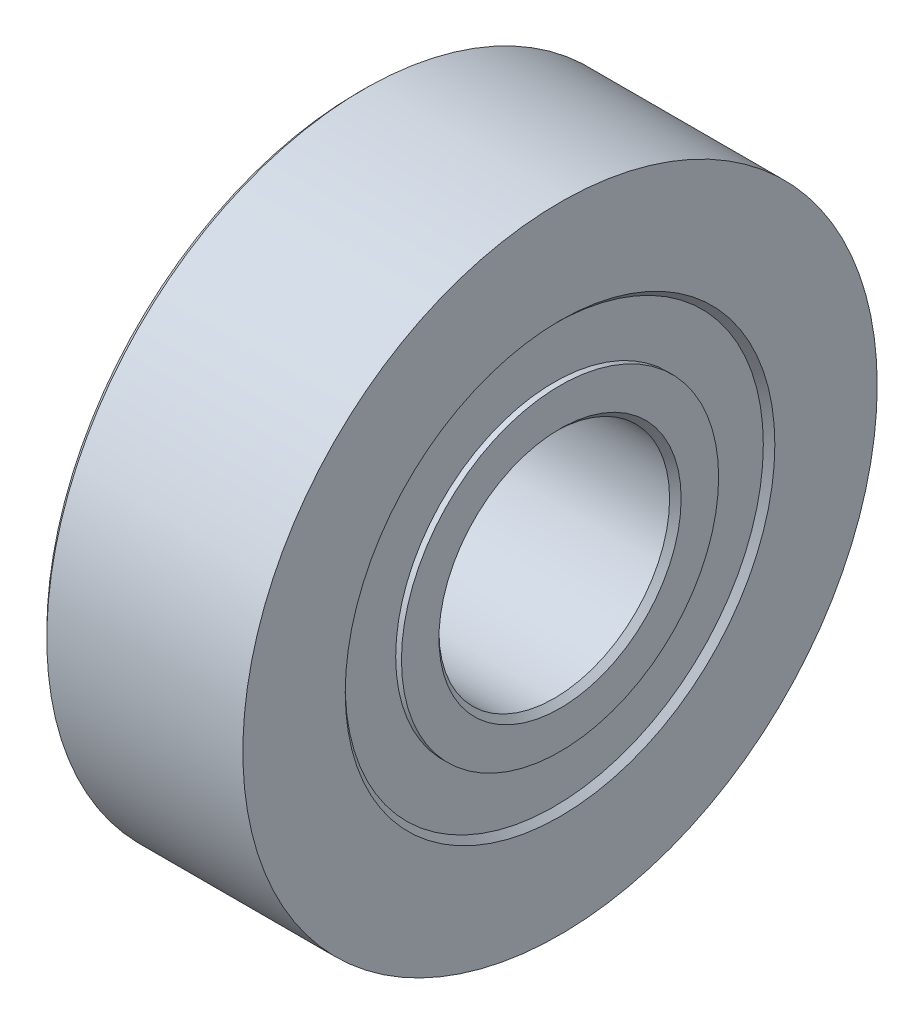
SolidWorks part; units mm, degrees
material "Chrome Stainless Steel"
ref_plane "Front Plane" through (0, 0, 0) normal (0, 0, 1) x (1, 0, 0)
ref_plane "Top Plane" through (0, 0, 0) normal (0, 1, 0) x (1, 0, 0)
ref_plane "Right Plane" through (0, 0, 0) normal (1, 0, 0) x (0, 0, -1)
sketch "Sketch2" plane through (0, 0, 0) normal (1, 0, 0) x (0, 0, -1)
  circle A0 centre (0, 0) radius 11
  dimension "D1" = 22
extrude "Boss-Extrude1" add sketch "Sketch2" along normal mid plane 7
sketch "Sketch3" plane through (3.5, 0, 0) normal (1, 0, 0) x (0, 0, -1)
  circle A0 centre (0, 0) radius 4
  dimension "D1" = 8
extrude "Cut-Extrude1" cut sketch "Sketch3" against normal through all
sketch "Sketch4" plane through (3.5, 0, 0) normal (1, 0, 0) x (0, 0, -1)
  circle A0 centre (0, 0) radius 5.5
  circle A1 centre (0, 0) radius 7.25
  circle A3 centre (0, 0) radius 4 construction
  dimension "D1" = 1.5
  dimension "D2" = 14.5
extrude "Cut-Extrude2" cut sketch "Sketch4" against normal blind 0.2
mirror "Mirror1" about plane through (0, 0, 0) normal (1, 0, 0) of "Cut-Extrude2"
chamfer "Chamfer1" distance 0.2 angle 45 4 edges at (-3.5, 0, -4) (3.5, 0, -7.25) (3.5, 0, -4) (-3.5, 0, -11)
